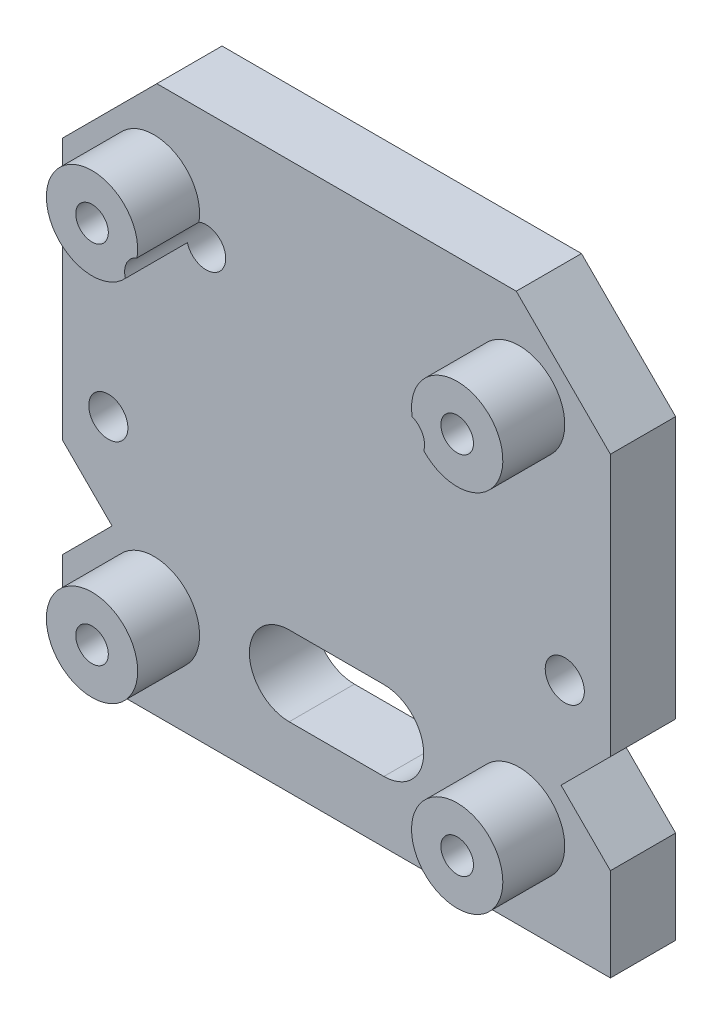
SolidWorks part; units mm, degrees
ref_plane "Front Plane" through (0, 0, 0) normal (0, 0, 1) x (1, 0, 0)
ref_plane "Top Plane" through (0, 0, 0) normal (0, 1, 0) x (1, 0, 0)
ref_plane "Right Plane" through (0, 0, 0) normal (1, 0, 0) x (0, 0, -1)
sketch "Sketch1" plane through (0, 0, 0) normal (0, 0, 1) x (1, 0, 0)
  line L1 (-14, -14) -> (14, -14) construction
  line L2 (-14, -14) -> (-14, 14) construction
  line L3 (-14, 14) -> (14, 14) construction
  line L4 (14, -14) -> (14, 14) construction
  line L5 (-14, -14) -> (14, 14) construction
  line L6 (-14, 14) -> (14, -14) construction
  line L7 (-21, -21) -> (21, -21)
  line L8 (-21, -21) -> (-21, 21)
  line L9 (-21, 21) -> (21, 21)
  line L10 (21, -21) -> (21, 21)
  line L11 (-21, -21) -> (21, 21) construction
  line L12 (-21, 21) -> (21, -21) construction
  circle A0 centre (-14, 14) radius 1.25
  circle A1 centre (14, 14) radius 1.25
  circle A2 centre (14, -14) radius 1.25
  circle A3 centre (-14, -14) radius 1.25
  point P0 (0, 0)
  point P10 (0, 0)
  dimension "D2" = 2.5
  dimension "D1" = 28
  dimension "D3" = 42
extrude "Boss-Extrude1" add sketch "Sketch1" against normal blind 5
sketch "Sketch2" plane through (0, 0, 0) normal (0, 0, 1) x (1, 0, 0)
  line L0 (-3.6316, -13.2494) -> (3.6312, -13.2494) construction
  line L1 (-3.6316, -10.1988) -> (3.6312, -10.1988)
  line L2 (-3.6316, -16.3) -> (3.6312, -16.3)
  arc A0 (-3.6316, -10.1988) -> (-3.6316, -16.3) centre (-3.6316, -13.2494) ccw
  arc A1 (3.6312, -16.3) -> (3.6312, -10.1988) centre (3.6312, -13.2494) ccw
  point P2 (-0.0002, -13.2494)
  point P7 (0, 0)
  point P10 (0, 0)
  point P11 (0, -13.2494)
extrude "Cut-Extrude1" cut sketch "Sketch2" against normal through all
sketch "Sketch3" plane through (0, 0, 0) normal (0, 0, 1) x (1, 0, 0)
  circle A0 centre (-14, 14) radius 3.5
  circle A1 centre (14, 14) radius 3.5
  circle A2 centre (-14, -14) radius 3.5
  circle A3 centre (14, -14) radius 3.5
  circle A4 centre (-14, 14) radius 1.25
  circle A5 centre (-14, 14) radius 1.25 construction
  circle A6 centre (14, 14) radius 1.25
  circle A7 centre (14, -14) radius 1.25
  circle A8 centre (-14, -14) radius 1.25
  dimension "D1" = 7
extrude "Boss-Extrude2" add sketch "Sketch3" along normal blind 4.75
sketch "Sketch4" plane through (0, 0, 0) normal (0, 0, 1) x (1, 0, 0)
  line L0 (-22.0267, -5.276) -> (-17.2138, -10.089)
  line L1 (-17.2138, -10.089) -> (-22.0267, -14.9019)
  line L2 (-22.0267, -14.9019) -> (-22.0267, -5.276)
  line L3 (0, -9.2674) -> (0, 0) construction
  line L4 (-21.7053, 13.0758) -> (-13.2553, 21.5258)
  line L5 (-13.2553, 21.5258) -> (-21.7053, 21.5258)
  line L6 (-21.7053, 21.5258) -> (-21.7053, 13.0758)
  circle A0 centre (-17.5, -2.9743) radius 1.5
  circle A1 centre (-10, 12.0257) radius 1.5
  point P11 (0, 0)
  point P14 (0, 0)
  point P15 (0, 0)
  point P16 (-9.3275, 11.991)
  point P17 (0, 0)
  point P18 (-16.8934, -9.5847)
  point P19 (-17.2138, -10.089)
  point P20 (-10, 12.0257)
  point P21 (-14.0461, 0.7689)
  point P22 (-17.5, -2.9743)
  point P23 (0, 0)
  dimension "D2" = 3
  dimension "D1" = 45
extrude "Cut-Extrude2" cut sketch "Sketch4" against normal through all both and the other way through all
mirror "Mirror1" about plane through (0, 0, 0) normal (1, 0, 0) of "Cut-Extrude2"
